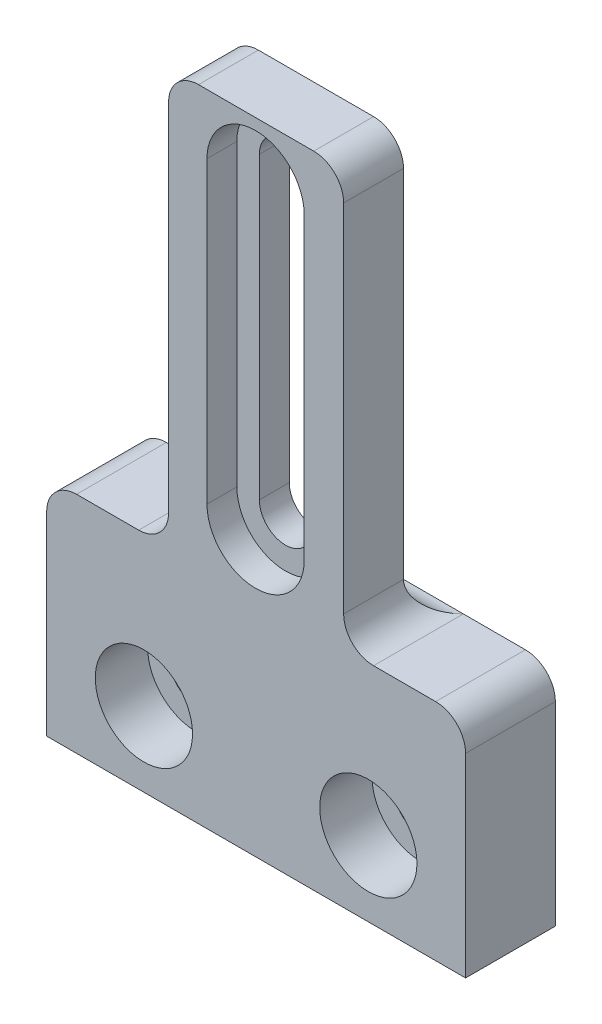
SolidWorks part; units mm, degrees
ref_plane "Front Plane" through (0, 0, 0) normal (0, 0, 1) x (1, 0, 0)
ref_plane "Top Plane" through (0, 0, 0) normal (0, 1, 0) x (1, 0, 0)
ref_plane "Right Plane" through (0, 0, 0) normal (1, 0, 0) x (0, 0, -1)
sketch "Sketch2" plane through (0, 0, 0) normal (0, 0, 1) x (1, 0, 0)
  line L1 (-28, 15) -> (0, 15)
  line L2 (-28, 15) -> (-28, 0)
  line L3 (-28, 0) -> (0, 0)
  line L4 (0, 15) -> (0, 0)
  dimension "D1" = 28
  dimension "D2" = 15
extrude "Boss-Extrude1" add sketch "Sketch2" along normal blind 6
sketch "Sketch3" plane through (0, 0, 6) normal (0, 0, 1) x (1, 0, 0)
  line L0 (-28, 15) -> (-28, 0) construction
  line L1 (0, 0) -> (0, 15) construction
  line L2 (0, 15) -> (-28, 15) construction
  circle A0 centre (-21.5, 5) radius 1.75
  circle A1 centre (-6.5, 5) radius 1.75
  dimension "D5" = 3.5
  dimension "D6" = 3.5
  dimension "D1" = 6.5
  dimension "D3" = 6.5
  dimension "D11" = 10
  dimension "D12" = 10
extrude "Cut-Extrude1" cut sketch "Sketch3" against normal through all both and the other way through all
sketch "Sketch6" plane through (0, 0, 6) normal (0, 0, 1) x (1, 0, 0)
  circle A0 centre (-21.5, 5) radius 3.25
  circle A1 centre (-6.5, 5) radius 3.25
  dimension "D1" = 6.5
  dimension "D2" = 6.5
extrude "Cut-Extrude2" cut sketch "Sketch6" against normal blind 3.5
sketch "Sketch7" plane through (0, 0, 0) normal (0, 0, -1) x (-1, 0, 0)
  line L0 (0, 15) -> (28, 15) construction
  line L1 (8.15, 15) -> (19.85, 15)
  line L2 (8.15, 15) -> (8.15, 42.7867)
  line L3 (8.15, 42.7867) -> (19.85, 42.7867)
  line L4 (19.85, 15) -> (19.85, 42.7867)
  line L5 (0, 0) -> (0, 15) construction
  dimension "D1" = 11.7
  dimension "D2" = 8.15
extrude "Boss-Extrude2" add sketch "Sketch7" against normal blind 6
sketch "Sketch8" plane through (0, 0, 0) normal (0, 0, -1) x (-1, 0, 0)
  line L0 (19.85, 15) -> (19.85, 42.7867) construction
  line L1 (8.15, 42.7867) -> (19.85, 42.7867)
  line L2 (8.15, 42.7867) -> (8.15, 15)
  line L3 (8.15, 15) -> (19.85, 15)
  line L4 (19.85, 42.7867) -> (19.85, 15)
extrude "Cut-Extrude3" cut sketch "Sketch8" against normal blind 2
fillet "Fillet1" radius 2 1 edges at (-14, 15, 2)
fillet "Fillet2" radius 2 1 edges at (-8.15, 15, 3)
fillet "Fillet3" radius 2 1 edges at (-19.85, 15, 3)
sketch "Sketch9" plane through (0, 0, 6) normal (0, 0, 1) x (1, 0, 0)
  line L0 (-14.0349, 38.7867) -> (-14.0349, 18.7867) construction
  line L1 (-12.2849, 38.7867) -> (-12.2849, 18.7867)
  line L2 (-15.7849, 38.7867) -> (-15.7849, 18.7867)
  line L3 (-19.85, 42.7867) -> (-8.15, 42.7867) construction
  arc A0 (-12.2849, 38.7867) -> (-15.7849, 38.7867) centre (-14.0349, 38.7867) ccw
  arc A1 (-15.7849, 18.7867) -> (-12.2849, 18.7867) centre (-14.0349, 18.7867) ccw
  point P2 (-14.0349, 28.7867)
  dimension "D1" = 3.5
  dimension "D2" = 20
  dimension "D3" = 4
extrude "Cut-Extrude4" cut sketch "Sketch9" against normal through all both and the other way through all
sketch "Sketch10" plane through (0, 0, 6) normal (0, 0, 1) x (1, 0, 0)
  line L0 (-14.0349, 38.7867) -> (-14.0349, 18.7867) construction
  line L1 (-10.7849, 38.7867) -> (-10.7849, 18.7867)
  line L2 (-17.2849, 38.7867) -> (-17.2849, 18.7867)
  arc A0 (-10.7849, 38.7867) -> (-17.2849, 38.7867) centre (-14.0349, 38.7867) ccw
  arc A1 (-17.2849, 18.7867) -> (-10.7849, 18.7867) centre (-14.0349, 18.7867) ccw
  point P4 (-14.0349, 28.7867)
  dimension "D1" = 6.5
extrude "Cut-Extrude5" cut sketch "Sketch10" against normal blind 2 and the other way through all
fillet "Fillet4" radius 2 2 edges at (-8.15, 42.7867, 4) (-19.85, 42.7867, 4)
fillet "Fillet5" radius 2 2 edges at (0, 15, 3) (-28, 15, 3)
